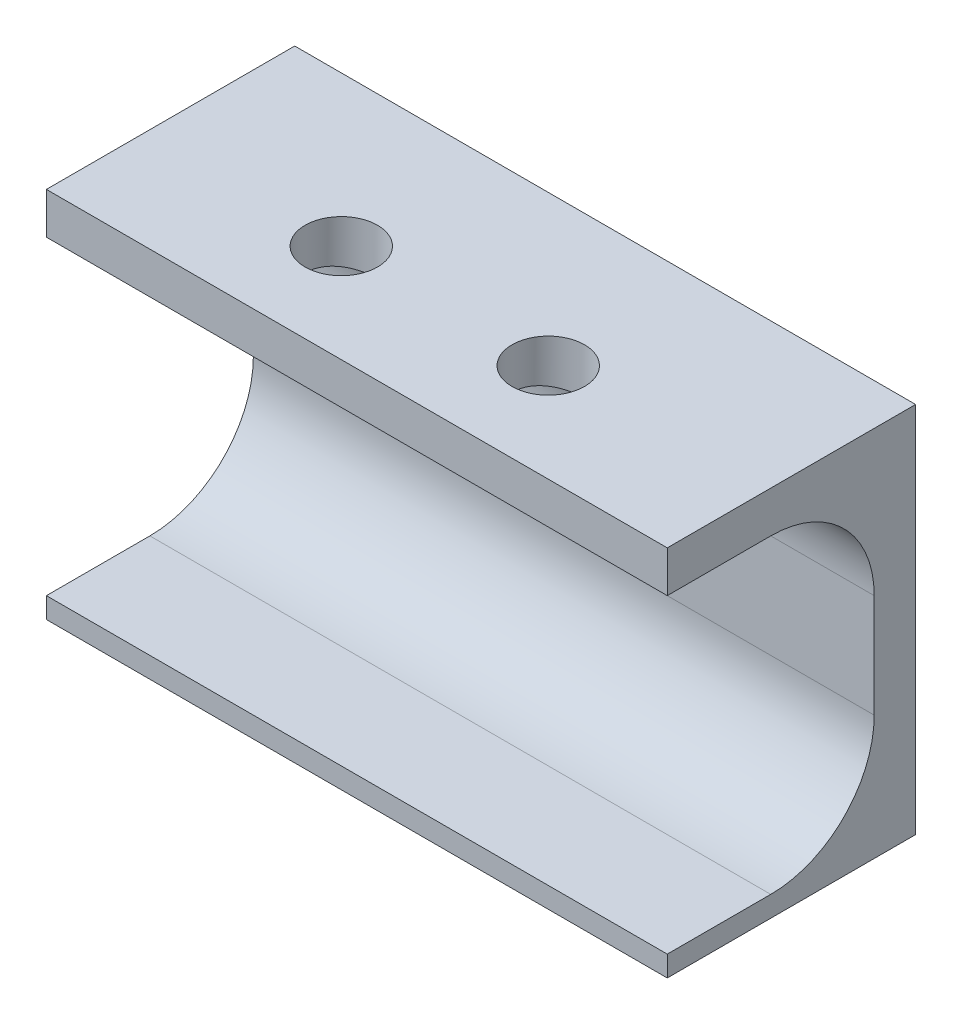
SolidWorks part; units mm, degrees
ref_plane "Front Plane" through (0, 0, 0) normal (0, 0, 1) x (1, 0, 0)
ref_plane "Top Plane" through (0, 0, 0) normal (0, 1, 0) x (1, 0, 0)
ref_plane "Right Plane" through (0, 0, 0) normal (1, 0, 0) x (0, 0, -1)
sketch "Sketch1" plane through (0, 0, 0) normal (1, 0, 0) x (0, 0, -1)
  line L0 (-6.5391, 14.6096) -> (-11.5391, 14.6096)
  line L1 (-11.5391, -1.3904) -> (0.4609, -1.3904)
  line L2 (-11.5391, -1.3904) -> (-11.5391, -0.3904)
  line L3 (-11.5391, 16.6096) -> (0.4609, 16.6096)
  line L4 (0.4609, -1.3904) -> (0.4609, 16.6096)
  line L7 (-6.5391, -0.3904) -> (-8.5391, -0.3904)
  line L8 (-1.5391, 4.6096) -> (-1.5391, 9.6096)
  line L11 (-8.5391, -0.3904) -> (-11.5391, -0.3904)
  line L12 (-11.5391, 14.6096) -> (-11.5391, 16.6096)
  arc A2 (-6.5391, -0.3904) -> (-1.5391, 4.6096) centre (-6.5391, 4.6096) ccw
  arc A5 (-1.5391, 9.6096) -> (-6.5391, 14.6096) centre (-6.5391, 9.6096) ccw
  point P6 (-10.2458, 6.3708)
  point P13 (-13.5391, 14.6096)
  point P18 (-1.5391, 14.6096)
  dimension "D4" = 2
  dimension "D7" = 5
  dimension "D1" = 18
  dimension "D2" = 12
  dimension "D3" = 1
  dimension "D6" = 12
extrude "Boss-Extrude1" add sketch "Sketch1" along normal blind 30
sketch "Sketch2" plane through (0, 16.6096, 0) normal (0, 1, 0) x (1, 0, 0)
  line L0 (30, 0.4609) -> (30, -11.5391) construction
  line L2 (30, -11.5391) -> (0, -11.5391) construction
  circle A0 centre (-10.5, -6.7891) radius 1.75
  circle A1 centre (-20.5, -6.7891) radius 1.75
  circle A2 centre (9.5, -6.7891) radius 1.75
  circle A3 centre (19.5, -6.7891) radius 1.75
  dimension "D1" = 3.5
  dimension "D2" = 10
  dimension "D3" = 10
  dimension "D4" = 20
  dimension "D5" = 10.5
  dimension "D6" = 4.75
  dimension "D7" = 4.75
  dimension "D8" = 4.75
  dimension "D9" = 4.75
extrude "Cut-Extrude1" cut sketch "Sketch2" against normal blind 5
